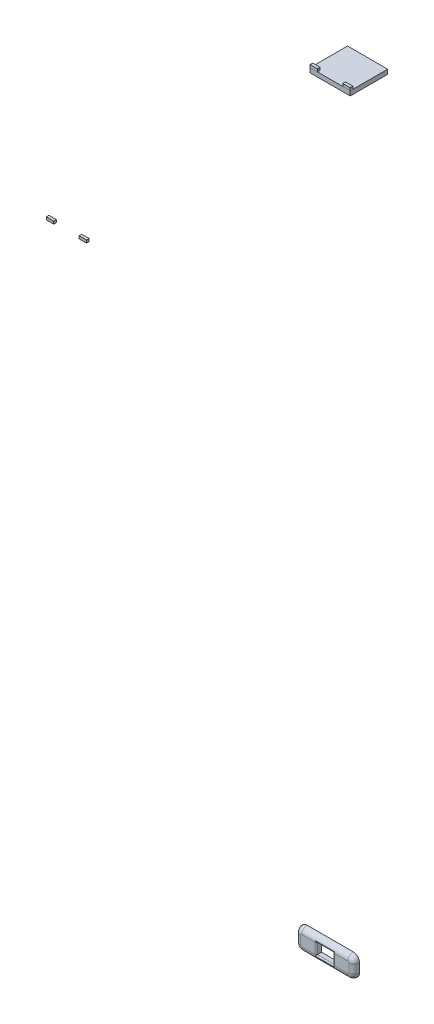
SolidWorks part; units mm, degrees
ref_plane "Спереди" through (0, 0, 0) normal (0, 0, 1) x (1, 0, 0)
ref_plane "Сверху" through (0, 0, 0) normal (0, 1, 0) x (1, 0, 0)
ref_plane "Справа" through (0, 0, 0) normal (1, 0, 0) x (0, 0, -1)
ref_plane "Плоскость4" through (0, 0, 173.9484) normal (0, 0, 1) x (1, 0, 0)
sketch "Эскиз1" plane through (0, 0, 173.9484) normal (0, 0, 1) x (1, 0, 0)
  line L1 (-208.0776, -72.8681) -> (-122.0776, -72.8681)
  line L2 (-220.0776, -84.8681) -> (-220.0776, -100.8681)
  line L3 (-208.0776, -112.8681) -> (-122.0776, -112.8681)
  line L4 (-110.0776, -84.8681) -> (-110.0776, -100.8681)
  arc A0 (-122.0776, -112.8681) -> (-110.0776, -100.8681) centre (-122.0776, -100.8681) ccw
  arc A1 (-122.0776, -72.8681) -> (-110.0776, -84.8681) centre (-122.0776, -84.8681) cw
  arc A2 (-220.0776, -100.8681) -> (-208.0776, -112.8681) centre (-208.0776, -100.8681) ccw
  arc A3 (-208.0776, -72.8681) -> (-220.0776, -84.8681) centre (-208.0776, -84.8681) ccw
  point P6 (-110.0776, -112.8681)
  point P11 (-220.0776, -112.8681)
  point P14 (-220.0776, -72.8681)
  dimension "D3" = 12
  dimension "D1" = 110
  dimension "D2" = 40
extrude "Бобышка-Вытянуть1" add sketch "Эскиз1" along normal blind 10
sketch "Эскиз2" plane through (0, 0, 183.9484) normal (0, 0, 1) x (1, 0, 0)
  line L8 (-220.0776, -92.8681) -> (-110.0776, -92.8681) construction
  line L9 (-220.0776, -84.8681) -> (-220.0776, -100.8681) construction
  line L10 (-110.0776, -100.8681) -> (-110.0776, -84.8681) construction
  line L11 (-165.0776, -72.8681) -> (-165.0776, -112.8681) construction
  line L12 (-122.0776, -72.8681) -> (-208.0776, -72.8681) construction
  line L13 (-208.0776, -112.8681) -> (-122.0776, -112.8681) construction
  line L18 (-181.0776, -82.7081) -> (-181.0776, -103.0281)
  line L19 (-181.0776, -103.0281) -> (-149.0776, -103.0281)
  line L20 (-149.0776, -103.0281) -> (-149.0776, -82.7081)
  line L21 (-149.0776, -82.7081) -> (-181.0776, -82.7081)
  point P2 (-181.0776, -92.8681)
  point P16 (-165.0776, -82.7081)
  dimension "D1" = 20.32
  dimension "D2" = 20.32
  dimension "D3" = 32
extrude "Вырез-Вытянуть1" cut sketch "Эскиз2" against normal up to surface (10 mm away) up to face at (-165.0776, -92.8681, 173.9484)
ref_plane "Плоскость5" through (-165.0776, 0, 0) normal (1, 0, 0) x (0, 0, -1)
ref_plane "Плоскость6" through (0, -103.0281, 0) normal (0, 1, 0) x (1, 0, 0)
ref_plane "Плоскость7" through (0, 0, 173.9484) normal (0, 0, -1) x (-1, 0, 0)
fillet "Скругление1" radius 10 8 edges at (-110.0776, -92.8681, 183.9484) (-113.5923, -109.3534, 183.9484) (-165.0776, -112.8681, 183.9484) (-216.5629, -109.3534, 183.9484) (-220.0776, -92.8681, 183.9484) (-216.5629, -76.3828, 183.9484) (-165.0776, -72.8681, 183.9484) (-113.5923, -76.3828, 183.9484)
fillet "Скругление2" radius 2 8 edges at (-149.0776, -102.9481, 183.9481) (-149.0776, -82.7881, 183.9481) (-181.0776, -82.7881, 183.9481) (-181.0776, -102.9481, 183.9481) (-149.0776, -92.8681, 183.9484) (-165.0776, -82.7081, 183.9471) (-181.0776, -92.8681, 183.9484) (-165.0776, -103.0281, 183.9471)
sketch "Эскиз3" plane through (0, 0, 173.9484) normal (0, 0, -1) x (-1, 0, 0)
  line L0 (181.717, 1316.8785) -> (134.647, 1316.8785) construction
  line L1 (127.5776, 1316.8785) -> (202.5776, 1316.8785)
  line L2 (127.5776, 1316.8785) -> (127.5776, 1308.507)
  line L3 (127.5776, 1308.507) -> (202.5776, 1308.507)
  line L4 (202.5776, 1316.8785) -> (202.5776, 1308.507)
  line L5 (165.0776, -72.8681) -> (165.0776, -133.1733) construction
  line L6 (122.0776, -72.8681) -> (208.0776, -72.8681) construction
  point P6 (165.0776, 1316.8785)
  dimension "D1" = 75
  dimension "D4" = 8.3715
extrude "Бобышка-Вытянуть2" add sketch "Эскиз3" along normal blind 70
sketch "Эскиз4" plane through (0, 1316.8785, 0) normal (0, 1, 0) x (1, 0, 0)
  line L0 (-202.5776, -103.9484) -> (-202.5776, -173.9484) construction
  line L1 (-202.5776, -661.5629) -> (-188.8126, -661.5629)
  line L2 (-202.5776, -661.5629) -> (-202.5776, -666.5629)
  line L3 (-202.5776, -666.5629) -> (-188.8126, -666.5629)
  line L4 (-188.8126, -661.5629) -> (-188.8126, -666.5629)
  line L5 (-141.3426, -661.5629) -> (-127.5776, -661.5629)
  line L6 (-141.3426, -661.5629) -> (-141.3426, -666.5629)
  line L7 (-141.3426, -666.5629) -> (-127.5776, -666.5629)
  line L8 (-127.5776, -661.5629) -> (-127.5776, -666.5629)
  line L9 (-202.5776, -168.9484) -> (-188.8126, -168.9484)
  line L10 (-202.5776, -168.9484) -> (-202.5776, -173.9484)
  line L11 (-202.5776, -173.9484) -> (-188.8126, -173.9484)
  line L12 (-188.8126, -168.9484) -> (-188.8126, -173.9484)
  line L13 (-122.0776, -173.9484) -> (-208.0776, -173.9484) construction
  line L14 (-127.5776, -103.9484) -> (-127.5776, -173.9484) construction
  line L15 (-141.3426, -173.9484) -> (-127.5776, -173.9484)
  line L16 (-141.3426, -173.9484) -> (-141.3426, -168.9484)
  line L17 (-141.3426, -168.9484) -> (-127.5776, -168.9484)
  line L18 (-127.5776, -173.9484) -> (-127.5776, -168.9484)
  dimension "D1" = 5
  dimension "D2" = 5
  dimension "D3" = 5
  dimension "D4" = 5
  dimension "D5" = 13.765
  dimension "D6" = 13.765
  dimension "D7" = 13.765
  dimension "D8" = 13.765
extrude "Бобышка-Вытянуть3" add sketch "Эскиз4" along normal blind 5
chamfer "Фаска1" distance 5 angle 45 rebuild error yes
sketch "Эскиз5" plane through (0, 1308.507, 0) normal (0, -1, 0) x (1, 0, 0)
  line L4 (-127.5776, 173.9484) -> (-202.5776, 173.9484)
  line L5 (-202.5776, 173.9484) -> (-202.5776, 103.9484)
  line L6 (-202.5776, 103.9484) -> (-127.5776, 103.9484)
  line L7 (-127.5776, 103.9484) -> (-127.5776, 173.9484)
  line L9 (-202.5776, 173.9484) -> (-202.5776, 103.9484)
  line L10 (-202.5776, 103.9484) -> (-127.5776, 103.9484)
  line L11 (-127.5776, 103.9484) -> (-127.5776, 173.9484)
  line L12 (-127.5776, 173.9484) -> (-202.5776, 173.9484)
  dimension "D1" = 0
extrude "Вырез-Вытянуть2" cut sketch "Эскиз5" against normal blind 3 rebuild error yes
